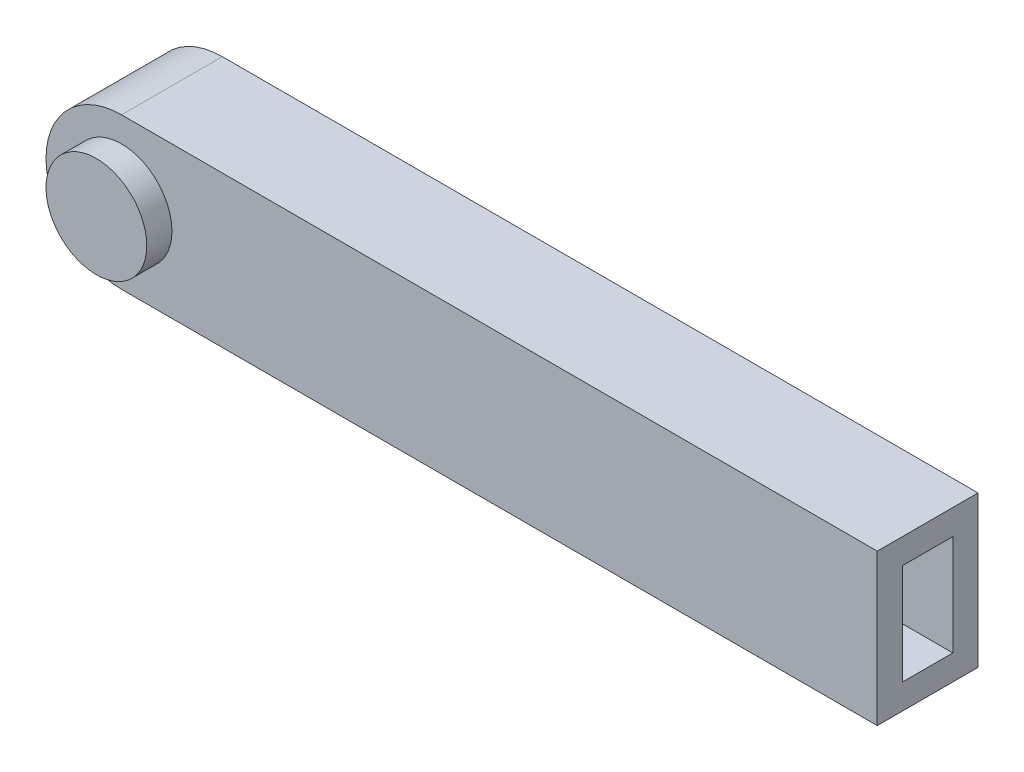
SolidWorks part; units mm, degrees
ref_plane "Front Plane" through (0, 0, 0) normal (0, 0, 1) x (1, 0, 0)
ref_plane "Top Plane" through (0, 0, 0) normal (0, 1, 0) x (1, 0, 0)
ref_plane "Right Plane" through (0, 0, 0) normal (1, 0, 0) x (0, 0, -1)
sketch "Sketch1" plane through (0, 0, 0) normal (0, 0, 1) x (1, 0, 0)
  line L0 (0, 0) -> (-300, 0)
  line L1 (0, 0) -> (0, 60)
  line L3 (0, 60) -> (-300, 60)
  circle A0 centre (-300, 30) radius 20
  arc A1 (-300, 60) -> (-300, 0) centre (-300, 30) ccw
  dimension "D1" = 40
  dimension "D2" = 60
extrude "Boss-Extrude1" add sketch "Sketch1" against normal blind 40 contours A0 | L3 A1 L0 L1 A0 region at (-152.289, 30, 0) region at (-300, 30, 0)
shell "Shell1" thickness 10 removed face at (0, 30, -20)
extrude "Boss-Extrude2" add sketch "Sketch1<3>" along normal blind 10 contours A0 region at (-300, 30, 0)
sketch "Sketch1<3>" plane through (0, 0, 0) normal (0, 0, 1) x (1, 0, 0) same geometry as "Sketch1"
sketch "Sketch2" plane through (0, 0, -40) normal (0, 0, -1) x (-1, 0, 0)
  circle A0 centre (300, 30) radius 20
  dimension "D1" = 40
extrude "Boss-Extrude3" add sketch "Sketch2" along normal blind 10
